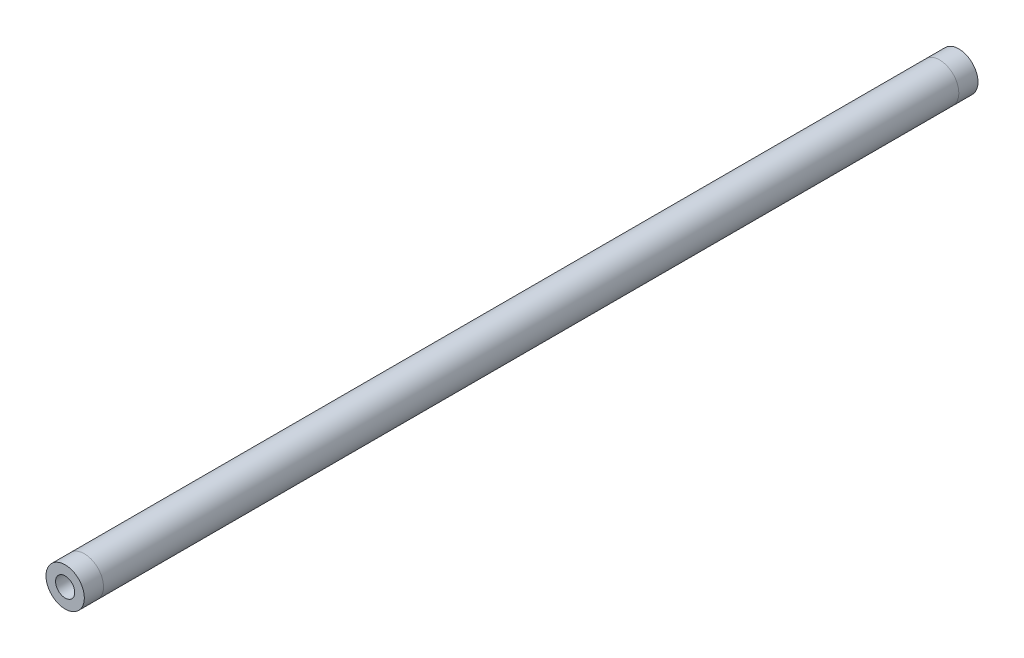
SolidWorks part; units mm, degrees
material "AISI 4130 Steel, normalized at 870C"
ref_plane "Front Plane" through (0, 0, 0) normal (0, 0, 1) x (1, 0, 0)
ref_plane "Top Plane" through (0, 0, 0) normal (0, 1, 0) x (1, 0, 0)
ref_plane "Right Plane" through (0, 0, 0) normal (1, 0, 0) x (0, 0, -1)
sketch "Axis" plane through (0, 0, 0) normal (0, 1, 0) x (1, 0, 0)
  line L0 (0, 0) -> (0, 21.9075) construction
  line L1 (0, 21.9075) -> (0, 317.7011) construction
  line L2 (0, 317.7011) -> (0, 339.6086) construction
  dimension "D1" = 21.9075
  dimension "D2" = 339.6086
sketch "Sketch2" plane through (0, 0, 0) normal (0, 0, 1) x (1, 0, 0)
  circle A0 centre (0, 0) radius 6.35
  circle A1 centre (0, 0) radius 3.175
  circle A2 centre (0, 0) radius 4.7625
  dimension "D1" = 12.7
  dimension "D2" = 6.35
  dimension "D3" = 9.525
extrude "Threaded Insert 1-1" add sketch "Sketch2" against normal blind 6.35 from vertex contours A0 A2 | A2 A1 region at (-6.1704, 0, 0) region at (-4.6278, 0, 0) starting at point (0, 0, -21.9075)
extrude "Threaded Insert 1-2" add sketch "Sketch2<5>" against normal blind 6.35 from surface contours A2 A1 region at (-4.6278, 0, 0) starting at face at (6.35, 0, -28.2575)
sketch "Sketch2<5>" plane through (0, 0, 0) normal (0, 0, 1) x (1, 0, 0) same geometry as "Sketch2"
extrude "Boss-Extrude4" add sketch "Sketch2<7>" along normal blind 6.35 from vertex separate body contours A0 A2 | A2 A1 region at (-6.1704, 0, 0) region at (-4.6278, 0, 0) starting at point (0, 0, -317.7011)
sketch "Sketch2<7>" plane through (0, 0, 0) normal (0, 0, 1) x (1, 0, 0) same geometry as "Sketch2"
extrude "Boss-Extrude5" add sketch "Sketch2<8>" along normal blind 6.35 from surface contours A2 A1 region at (-4.6278, 0, 0) starting at face at (6.35, 0, -311.3511)
sketch "Sketch2<8>" plane through (0, 0, 0) normal (0, 0, 1) x (1, 0, 0) same geometry as "Sketch2"
extrude "Boss-Extrude6" add sketch "Sketch2<9>" against normal up to surface (311.3511 mm away) from surface separate body contours A0 A2 region at (-6.1704, 0, 0) up to face at (6.35, 0, -311.3511) starting at face at (4.7625, 0, -28.2575)
sketch "Sketch2<9>" plane through (0, 0, 0) normal (0, 0, 1) x (1, 0, 0) same geometry as "Sketch2"
equation "\"Tube Outer Diameter\"= .5"
equation "\"Tube Inner Diameter\"= .375"
equation "\"Rod end Diameter\"= .25"
equation "\"Threaded Insert Out\"= .25"
equation "\"Threaded Insert In\"= .25'`"
equation "\"D1@Sketch2\"=\"Tube Outer Diameter\""
equation "\"D2@Sketch2\"=\"Rod end Diameter\""
equation "\"D1@Threaded Insert 1-1\" = \"Threaded Insert Out\""
equation "\"D3@Sketch2\"=\"Tube Inner Diameter\""
equation "\"D1@Threaded Insert 1-2\" = \"Threaded Insert In\""
equation "\"D1@Boss-Extrude4\"=\"Threaded Insert Out\""
equation "\"D1@Boss-Extrude5\"=\"Threaded Insert In\""
